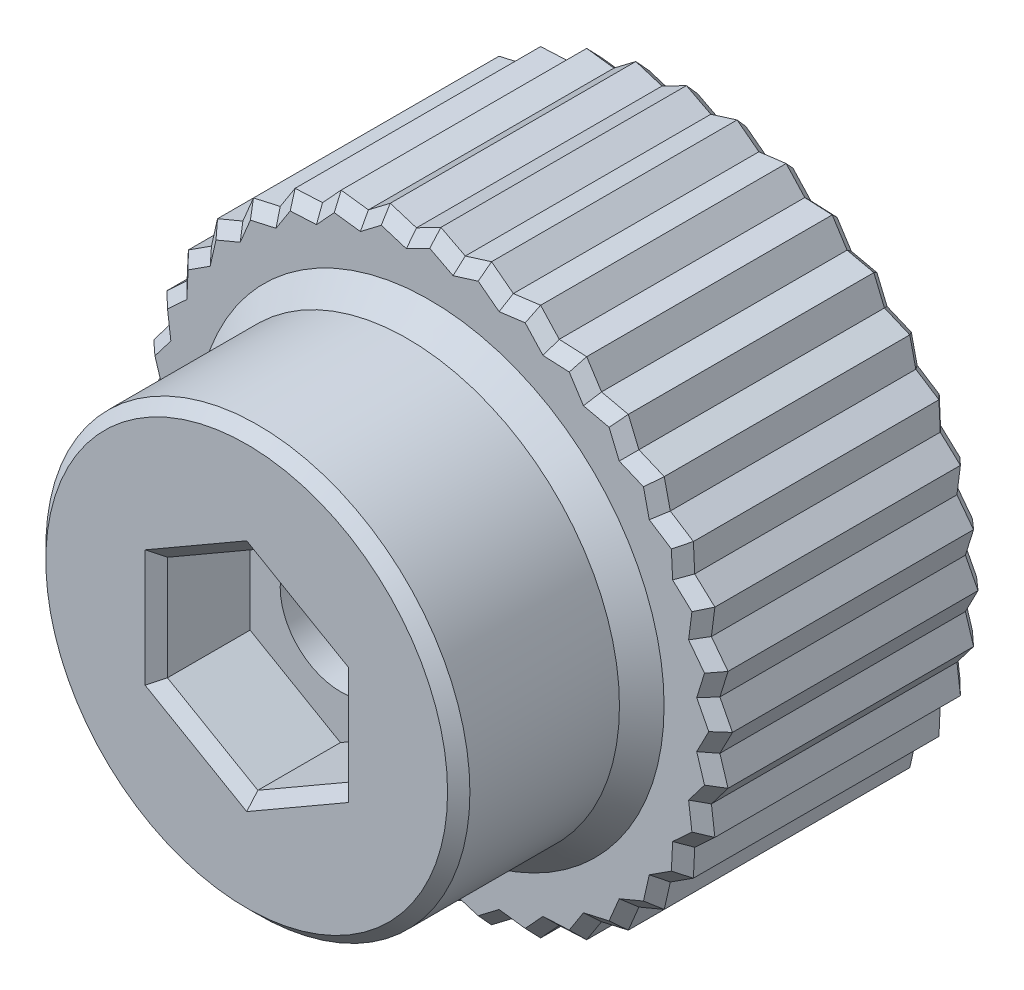
SolidWorks part; units mm, degrees
note: The reader was unsure of these and kept them because the rebuilt part matched: shared geometry of "Sketch9<3>".
ref_plane "Front Plane (Z)" through (0, 0, 0) normal (0, 0, 1) x (1, 0, 0)
ref_plane "Top Plane (Y)" through (0, 0, 0) normal (0, 1, 0) x (1, 0, 0)
ref_plane "Side Plane (X)" through (0, 0, 0) normal (1, 0, 0) x (0, 0, -1)
sketch "Sketch1" plane through (0, 0, 0) normal (0, 0, 1) x (1, 0, 0)
  circle A1 centre (0, 0) radius 12.5
  dimension "D2" = 25
extrude "Boss-Extrude1" add sketch "Sketch1" along normal blind 12
sketch "Sketch5" plane through (0, 0, 12) normal (0, 0, 1) x (1, 0, 0)
  line L0 (0, 0) -> (0, 15.5343) construction
  line L1 (0, 13.0632) -> (1.0936, 12.4995)
  line L2 (0, 0) -> (1.0936, 12.4995) construction
  line L3 (0, 13.0632) -> (-1.0936, 12.4995)
  line L4 (2.2684, 12.8647) -> (1.0936, 12.4995)
  line L5 (2.2684, 12.8647) -> (3.2475, 12.1197)
  line L6 (4.4679, 12.2754) -> (3.2475, 12.1197)
  line L7 (4.4679, 12.2754) -> (5.3027, 11.3716)
  line L8 (6.5316, 11.3131) -> (5.3027, 11.3716)
  line L9 (6.5316, 11.3131) -> (7.1968, 10.2781)
  line L10 (8.3969, 10.007) -> (7.1968, 10.2781)
  line L11 (8.3969, 10.007) -> (8.8722, 8.8722)
  line L12 (10.007, 8.3969) -> (8.8722, 8.8722)
  line L13 (10.007, 8.3969) -> (10.2781, 7.1968)
  line L14 (11.3131, 6.5316) -> (10.2781, 7.1968)
  line L15 (11.3131, 6.5316) -> (11.3716, 5.3027)
  line L16 (12.2754, 4.4679) -> (11.3716, 5.3027)
  line L17 (12.2754, 4.4679) -> (12.1197, 3.2475)
  line L18 (12.8647, 2.2684) -> (12.1197, 3.2475)
  line L19 (12.8647, 2.2684) -> (12.4995, 1.0936)
  line L20 (13.0632, 0) -> (12.4995, 1.0936)
  line L21 (13.0632, 0) -> (12.4995, -1.0936)
  line L22 (12.8647, -2.2684) -> (12.4995, -1.0936)
  line L23 (12.8647, -2.2684) -> (12.1197, -3.2475)
  line L24 (12.2754, -4.4679) -> (12.1197, -3.2475)
  line L25 (12.2754, -4.4679) -> (11.3716, -5.3027)
  line L26 (11.3131, -6.5316) -> (11.3716, -5.3027)
  line L27 (11.3131, -6.5316) -> (10.2781, -7.1968)
  line L28 (10.007, -8.3969) -> (10.2781, -7.1968)
  line L29 (10.007, -8.3969) -> (8.8722, -8.8722)
  line L30 (8.3969, -10.007) -> (8.8722, -8.8722)
  line L31 (8.3969, -10.007) -> (7.1968, -10.2781)
  line L32 (6.5316, -11.3131) -> (7.1968, -10.2781)
  line L33 (6.5316, -11.3131) -> (5.3027, -11.3716)
  line L34 (4.4679, -12.2754) -> (5.3027, -11.3716)
  line L35 (4.4679, -12.2754) -> (3.2475, -12.1197)
  line L36 (2.2684, -12.8647) -> (3.2475, -12.1197)
  line L37 (2.2684, -12.8647) -> (1.0936, -12.4995)
  line L38 (0, -13.0632) -> (1.0936, -12.4995)
  line L39 (0, -13.0632) -> (-1.0936, -12.4995)
  line L40 (-2.2684, -12.8647) -> (-1.0936, -12.4995)
  line L41 (-2.2684, -12.8647) -> (-3.2475, -12.1197)
  line L42 (-4.4679, -12.2754) -> (-3.2475, -12.1197)
  line L43 (-4.4679, -12.2754) -> (-5.3027, -11.3716)
  line L44 (-6.5316, -11.3131) -> (-5.3027, -11.3716)
  line L45 (-6.5316, -11.3131) -> (-7.1968, -10.2781)
  line L46 (-8.3969, -10.007) -> (-7.1968, -10.2781)
  line L47 (-8.3969, -10.007) -> (-8.8722, -8.8722)
  line L48 (-10.007, -8.3969) -> (-8.8722, -8.8722)
  line L49 (-10.007, -8.3969) -> (-10.2781, -7.1968)
  line L50 (-11.3131, -6.5316) -> (-10.2781, -7.1968)
  line L51 (-11.3131, -6.5316) -> (-11.3716, -5.3027)
  line L52 (-12.2754, -4.4679) -> (-11.3716, -5.3027)
  line L53 (-12.2754, -4.4679) -> (-12.1197, -3.2475)
  line L54 (-12.8647, -2.2684) -> (-12.1197, -3.2475)
  line L55 (-12.8647, -2.2684) -> (-12.4995, -1.0936)
  line L56 (-13.0632, 0) -> (-12.4995, -1.0936)
  line L57 (-13.0632, 0) -> (-12.4995, 1.0936)
  line L58 (-12.8647, 2.2684) -> (-12.4995, 1.0936)
  line L59 (-12.8647, 2.2684) -> (-12.1197, 3.2475)
  line L60 (-12.2754, 4.4679) -> (-12.1197, 3.2475)
  line L61 (-12.2754, 4.4679) -> (-11.3716, 5.3027)
  line L62 (-11.3131, 6.5316) -> (-11.3716, 5.3027)
  line L63 (-11.3131, 6.5316) -> (-10.2781, 7.1968)
  line L64 (-10.007, 8.3969) -> (-10.2781, 7.1968)
  line L65 (-10.007, 8.3969) -> (-8.8722, 8.8722)
  line L66 (-8.3969, 10.007) -> (-8.8722, 8.8722)
  line L67 (-8.3969, 10.007) -> (-7.1968, 10.2781)
  line L68 (-6.5316, 11.3131) -> (-7.1968, 10.2781)
  line L69 (-6.5316, 11.3131) -> (-5.3027, 11.3716)
  line L70 (-4.4679, 12.2754) -> (-5.3027, 11.3716)
  line L71 (-4.4679, 12.2754) -> (-3.2475, 12.1197)
  line L72 (-2.2684, 12.8647) -> (-3.2475, 12.1197)
  line L73 (-2.2684, 12.8647) -> (-1.0936, 12.4995)
  circle A1 centre (0, 0) radius 12.0902
  point P115 (0, 0)
  dimension "D2" = 36
extrude "Boss-Extrude4" add sketch "Sketch5" against normal up to surface (12 mm away) up to face at (12.5, 0, 0)
sketch "Sketch8" plane through (0, 0, 12) normal (0, 0, 1) x (1, 0, 0)
  circle A0 centre (0, 0) radius 9.5
  dimension "D1" = 19
extrude "Boss-Extrude5" add sketch "Sketch8" along normal blind 8.2
sketch "Sketch9" plane through (0, 0, 0) normal (0, 0, -1) x (-1, 0, 0)
  circle A0 centre (0, 0) radius 2.7
  circle A1 centre (0, 0) radius 4.4
  dimension "D1" = 5.4
  dimension "D2" = 8.8
extrude "Cut-Extrude2" cut sketch "Sketch9" against normal through all contours A0
extrude "Cut-Extrude3" cut sketch "Sketch9<3>" against normal blind 5.2
sketch "Sketch9<3>" plane through (0, 0, 0) normal (0, 0, -1) x (-1, 0, 0) same geometry as "Sketch9"
sketch "Sketch10" plane through (0, 0, 20.2) normal (0, 0, 1) x (1, 0, 0)
  line L1 (0, 4.6765) -> (-4.05, 2.3383)
  line L2 (-4.05, 2.3383) -> (-4.05, -2.3383)
  line L3 (-4.05, -2.3383) -> (0, -4.6765)
  line L4 (0, -4.6765) -> (4.05, -2.3383)
  line L5 (4.05, -2.3383) -> (4.05, 2.3383)
  line L6 (4.05, 2.3383) -> (0, 4.6765)
  circle A0 centre (0, 0) radius 4.05 construction
  dimension "D1" = 8.1
extrude "Cut-Extrude4" cut sketch "Sketch10" against normal blind 4.2
chamfer "Chamfer2" distance 0.5 angle 45 152 edges at (-1.681, 12.6821, 0) (-2.7579, 12.4922, 0) (-3.8577, 12.1975, 0) (-4.8853, 11.8235, 0) (-5.9171, 11.3424, 0) (-6.8642, 10.7956, 0) (-7.7968, 10.1425, 0) (-8.6345, 9.4396, 0) (-9.4396, 8.6345, 0) (-10.1425, 7.7968, 0) (-10.7956, 6.8642, 0) (-11.3424, 5.9171, 0) (-11.8235, 4.8853, 0) (-12.1975, 3.8577, 0) (-12.4922, 2.7579, 0) (-12.6821, 1.681, 0) (-12.7813, 0.5468, 0) (-12.7813, -0.5468, 0) (-12.6821, -1.681, 0) (-12.4922, -2.7579, 0) (-12.1975, -3.8577, 0) (-11.8235, -4.8853, 0) (-11.3424, -5.9171, 0) (-10.7956, -6.8642, 0) (-10.1425, -7.7968, 0) (-9.4396, -8.6345, 0) (-8.6345, -9.4396, 0) (-7.7968, -10.1425, 0) (-6.8642, -10.7956, 0) (-5.9171, -11.3424, 0) (-4.8853, -11.8235, 0) (-3.8577, -12.1975, 0) (-2.7579, -12.4922, 0) (-1.681, -12.6821, 0) (-0.5468, -12.7813, 0) (0.5468, -12.7813, 0) (1.681, -12.6821, 0) (2.7579, -12.4922, 0) (3.8577, -12.1975, 0) (4.8853, -11.8235, 0) (5.9171, -11.3424, 0) (6.8642, -10.7956, 0) (7.7968, -10.1425, 0) (8.6345, -9.4396, 0) (9.4396, -8.6345, 0) (10.1425, -7.7968, 0) (10.7956, -6.8642, 0) (11.3424, -5.9171, 0) (11.8235, -4.8853, 0) (12.1975, -3.8577, 0) (12.4922, -2.7579, 0) (12.6821, -1.681, 0) (12.7813, -0.5468, 0) (12.7813, 0.5468, 0) (12.6821, 1.681, 0) (12.4922, 2.7579, 0) (12.1975, 3.8577, 0) (11.8235, 4.8853, 0) (11.3424, 5.9171, 0) (10.7956, 6.8642, 0) (10.1425, 7.7968, 0) (9.4396, 8.6345, 0) (8.6345, 9.4396, 0) (7.7968, 10.1425, 0) (6.8642, 10.7956, 0) (5.9171, 11.3424, 0) (4.8853, 11.8235, 0) (3.8577, 12.1975, 0) (2.7579, 12.4922, 0) (1.681, 12.6821, 0) (0.5468, 12.7813, 0) (-0.5468, 12.7813, 0) (0.5468, 12.7813, 12) (1.681, 12.6821, 12) (2.7579, 12.4922, 12) (3.8577, 12.1975, 12) (4.8853, 11.8235, 12) (5.9171, 11.3424, 12) (6.8642, 10.7956, 12) (7.7968, 10.1425, 12) (8.6345, 9.4396, 12) (9.4396, 8.6345, 12) (10.1425, 7.7968, 12) (10.7956, 6.8642, 12) (11.3424, 5.9171, 12) (11.8235, 4.8853, 12) (12.1975, 3.8577, 12) (12.4922, 2.7579, 12) (12.6821, 1.681, 12) (12.7813, 0.5468, 12) (12.7813, -0.5468, 12) (12.6821, -1.681, 12) (12.4922, -2.7579, 12) (12.1975, -3.8577, 12) (11.8235, -4.8853, 12) (11.3424, -5.9171, 12) (10.7956, -6.8642, 12) (10.1425, -7.7968, 12) (9.4396, -8.6345, 12) (8.6345, -9.4396, 12) (7.7968, -10.1425, 12) (6.8642, -10.7956, 12) (5.9171, -11.3424, 12) (4.8853, -11.8235, 12) (3.8577, -12.1975, 12) (2.7579, -12.4922, 12) (1.681, -12.6821, 12) (0.5468, -12.7813, 12) (-0.5468, -12.7813, 12) (-1.681, -12.6821, 12) (-2.7579, -12.4922, 12) (-3.8577, -12.1975, 12) (-4.8853, -11.8235, 12) (-5.9171, -11.3424, 12) (-6.8642, -10.7956, 12) (-7.7968, -10.1425, 12) (-8.6345, -9.4396, 12) (-9.4396, -8.6345, 12) (-10.1425, -7.7968, 12) (-10.7956, -6.8642, 12) (-11.3424, -5.9171, 12) (-11.8235, -4.8853, 12) (-12.1975, -3.8577, 12) (-12.4922, -2.7579, 12) (-12.6821, -1.681, 12) (-12.7813, -0.5468, 12) (-12.7813, 0.5468, 12) (-12.6821, 1.681, 12) (-12.4922, 2.7579, 12) (-12.1975, 3.8577, 12) (-11.8235, 4.8853, 12) (-11.3424, 5.9171, 12) (-10.7956, 6.8642, 12) (-10.1425, 7.7968, 12) (-9.4396, 8.6345, 12) (-8.6345, 9.4396, 12) (-7.7968, 10.1425, 12) (-6.8642, 10.7956, 12) (-5.9171, 11.3424, 12) (-4.8853, 11.8235, 12) (-3.8577, 12.1975, 12) (-2.7579, 12.4922, 12) (-1.681, 12.6821, 12) (-0.5468, 12.7813, 12) (-4.4, 0, 0) (9.5, 0, 20.2) (-2.025, 3.5074, 20.2) (-4.05, 0, 20.2) (-2.025, -3.5074, 20.2) (2.025, -3.5074, 20.2) (4.05, 0, 20.2) (2.025, 3.5074, 20.2)
chamfer "Chamfer3" distance 1 angle 45 1 edges at (9.5, 0, 12)
sketch "Sketch11" plane through (0, 0, 5.2) normal (0, 0, -1) x (-1, 0, 0)
  circle A0 centre (0, 0) radius 2.7
  circle A1 centre (0, 0) radius 2.7 construction
extrude "Boss-Extrude6" add sketch "Sketch11" against normal blind 0.2
